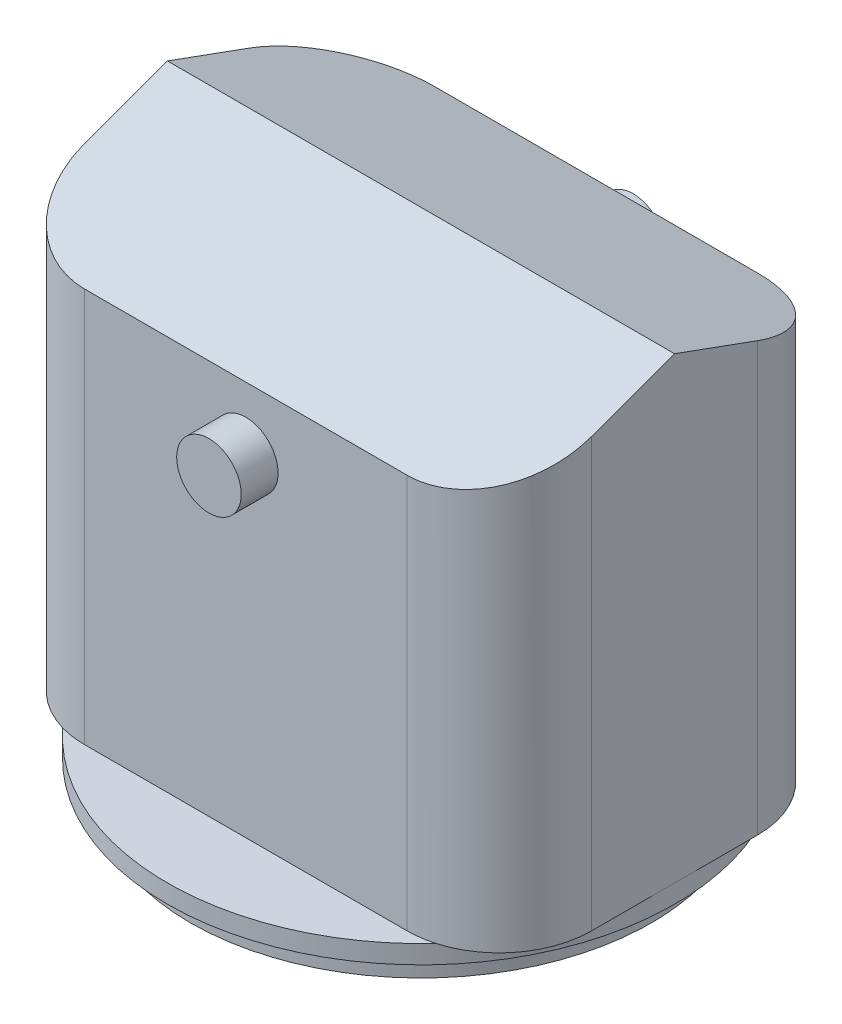
SolidWorks part; units mm, degrees
ref_plane "Ön Düzlem" through (0, 0, 0) normal (0, 0, 1) x (1, 0, 0)
ref_plane "Üst Düzlem" through (0, 0, 0) normal (0, 1, 0) x (1, 0, 0)
ref_plane "Sağ Düzlem" through (0, 0, 0) normal (1, 0, 0) x (0, 0, -1)
sketch "Çizim1" plane through (0, 0, 0) normal (0, 1, 0) x (1, 0, 0)
  circle A0 centre (0, 0) radius 27.5
  dimension "D1" = 55
extrude "Yükseklik-Ekstrüzyon1" add sketch "Çizim1" along normal blind 2
sketch "Çizim2" plane through (0, 0, 0) normal (0, -1, 0) x (1, 0, 0)
  circle A0 centre (0, 0) radius 23
  circle A1 centre (0, 0) radius 25
  dimension "D1" = 50
  dimension "D2" = 46
extrude "Yükseklik-Ekstrüzyon2" add sketch "Çizim2" along normal blind 3
sketch "Çizim3" plane through (0, 2, 0) normal (0, 1, 0) x (1, 0, 0)
  line L1 (-17.5, -19) -> (17.5, -19)
  line L2 (-27.5, -9) -> (-27.5, 9)
  line L3 (-17.5, 19) -> (17.5, 19)
  line L4 (27.5, -9) -> (27.5, 9)
  line L5 (-27.5, -19) -> (27.5, 19) construction
  line L6 (-27.5, 19) -> (27.5, -19) construction
  arc A1 (-17.5, -19) -> (-27.5, -9) centre (-17.5, -9) cw
  arc A2 (17.5, -19) -> (27.5, -9) centre (17.5, -9) ccw
  arc A3 (17.5, 19) -> (27.5, 9) centre (17.5, 9) cw
  arc A4 (-27.5, 9) -> (-17.5, 19) centre (-17.5, 9) cw
  point P0 (0, 0)
  dimension "D3" = 10
  dimension "D1" = 55
  dimension "D2" = 38
extrude "Yükseklik-Ekstrüzyon3" add sketch "Çizim3" along normal blind 50.8
chamfer "Pah1" distance 8 angle 70 1 edges at (0, 52.8, -19) first distance on face at (0, 27.4, -19)
chamfer "Pah2" distance 8 angle 70 1 edges at (0, 52.8, 19) first distance on face at (0, 27.4, 19)
sketch "Çizim4" plane through (0, 0, 19) normal (0, 0, 1) x (1, 0, 0)
  line L0 (0, 0) -> (0, 38) construction
  circle A0 centre (0, 38) radius 3.5
  dimension "D2" = 7
  dimension "D1" = 38
extrude "Yükseklik-Ekstrüzyon4" add sketch "Çizim4" along normal blind 4
sketch "Çizim5" plane through (0, 0, -19) normal (0, 0, -1) x (-1, 0, 0)
  line L0 (0, 0) -> (0, 38) construction
  circle A0 centre (0, 38) radius 3.5
  dimension "D2" = 7
  dimension "D1" = 38
extrude "Yükseklik-Ekstrüzyon5" add sketch "Çizim5" along normal blind 4
